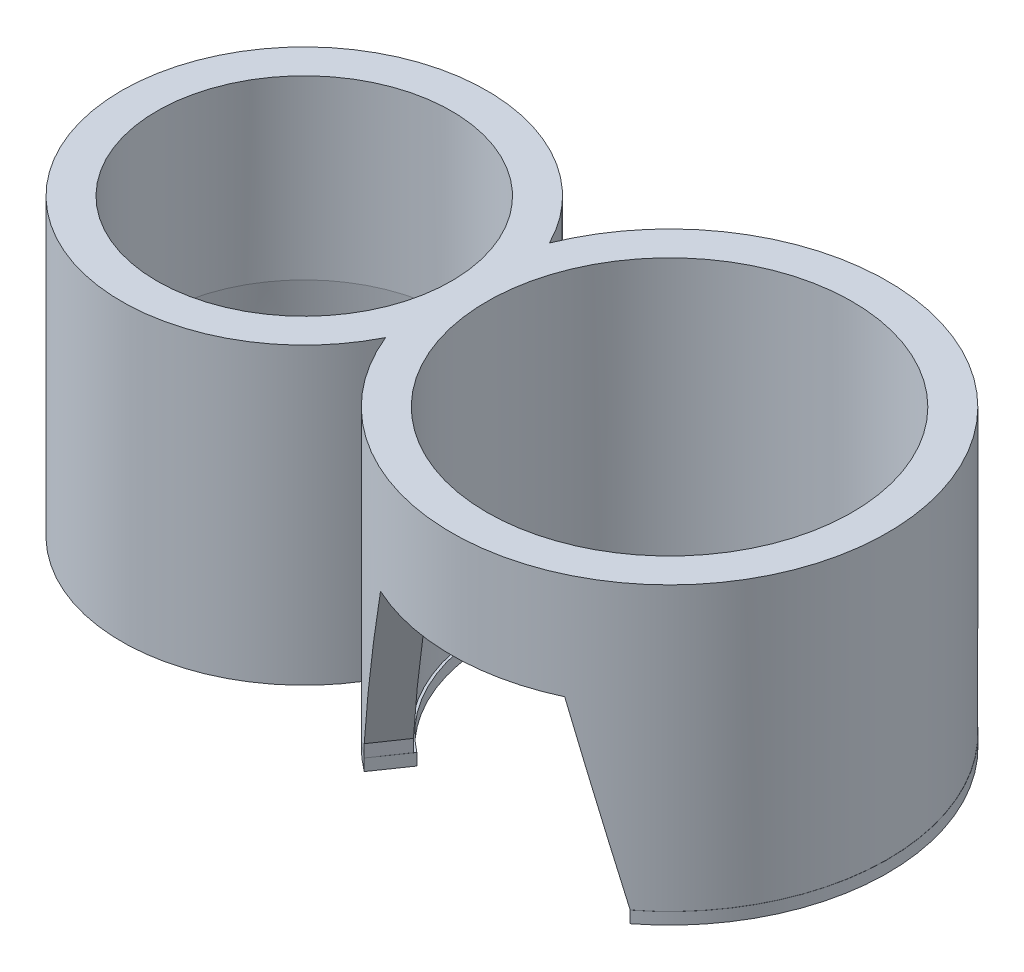
SolidWorks part; units mm, degrees
ref_plane "Front Plane" through (0, 0, 0) normal (0, 0, 1) x (1, 0, 0)
ref_plane "Top Plane" through (0, 0, 0) normal (0, 1, 0) x (1, 0, 0)
ref_plane "Right Plane" through (0, 0, 0) normal (1, 0, 0) x (0, 0, -1)
sketch "Esquisse2" plane through (0, 0, 0) normal (0, 1, 0) x (1, 0, 0)
  circle A0 centre (0, 0) radius 12.5
  circle A1 centre (0, 0) radius 15.5
  dimension "D1" = 25
  dimension "D2" = 31
extrude "Boss.-Extru.6" add sketch "Esquisse2" along normal blind 24 and the other way blind 1
sketch "Esquisse3" plane through (0, 0, 0) normal (0, 1, 0) x (1, 0, 0)
  line L0 (0, 0) -> (31, 0) construction
  circle A0 centre (31, 0) radius 15.5
  circle A1 centre (31, 0) radius 18.5
  circle A2 centre (0, 0) radius 12.5 construction
  dimension "D1" = 31
  dimension "D2" = 37
extrude "Boss.-Extru.7" add sketch "Esquisse3" along normal blind 24
sketch "Esquisse6" plane through (0, 0, 0) normal (0, 1, 0) x (1, 0, 0)
  line L0 (31, 0) -> (31, -18.5) construction
  line L1 (21.5424, -12.2802) -> (40.4576, -12.2802) construction
  line L2 (31, 0) -> (21.5424, -12.2802) construction
  line L3 (21.5424, -12.2802) -> (40.4576, -12.2802) construction
  line L4 (40.4576, -12.2802) -> (31, 0) construction
  line L5 (21.5424, -12.2802) -> (19.8461, -14.7594)
  line L6 (40.4576, -12.2802) -> (42.2881, -14.657)
  arc A0 (13.8548, -6.9493) -> (13.8548, 6.9493) centre (31, 0) ccw construction
  circle A1 centre (31, 0) radius 15.5 construction
  arc A2 (21.5424, -12.2802) -> (40.4576, -12.2802) centre (31, 0) ccw
  arc A3 (19.8461, -14.7594) -> (42.2881, -14.657) centre (31, 0) ccw
extrude "Enlèv. mat.-Extru.4" cut sketch "Esquisse6" along normal blind 15 contours L5 A3 L6 A2 region at (31.0404, 0, 15.8541)
chamfer "Chanfrein3" distance 10 angle 5 1 edges at (0, -1, 12.5) first distance on face at (0, -1, 12.5)
chamfer "Chanfrein4" distance 4 angle 74 1 edges at (20.6943, 15, 13.5198) first distance on face at (31.0379, 15, 15.2471)
chamfer "Chanfrein5" distance 4 angle 75 1 edges at (41.3728, 15, 13.4686) first distance on face at (32.9035, 15, 15.6939)
sketch "Esquisse7" plane through (0, 0, 0) normal (0, 1, 0) x (1, 0, 0)
  circle A0 centre (31.0079, 0) radius 18.5
  point P2 (31.0079, 0)
  point P3 (0, 0)
sketch "Esquisse18" plane through (0, 0, 0) normal (0, 1, 0) x (1, 0, 0)
  line L0 (40.4576, -12.2802) -> (42.2881, -14.657) construction
  line L1 (40.3602, -12.1088) -> (42.2939, -14.6646)
  line L2 (21.6675, -12.118) -> (19.8461, -14.7594)
  arc A0 (21.6675, -12.118) -> (40.3602, -12.1088) centre (31.0079, 0) cw
  arc A1 (19.8461, -14.7594) -> (42.2939, -14.6646) centre (31.0079, 0) cw
  point P4 (21.5424, -12.2802)
  point P5 (41.5604, -13.7122)
  point P12 (39.7258, -11.3292)
  point P13 (40.4854, -12.2802)
extrude "Boss.-Extru.9" add sketch "Esquisse18" against normal blind 1
